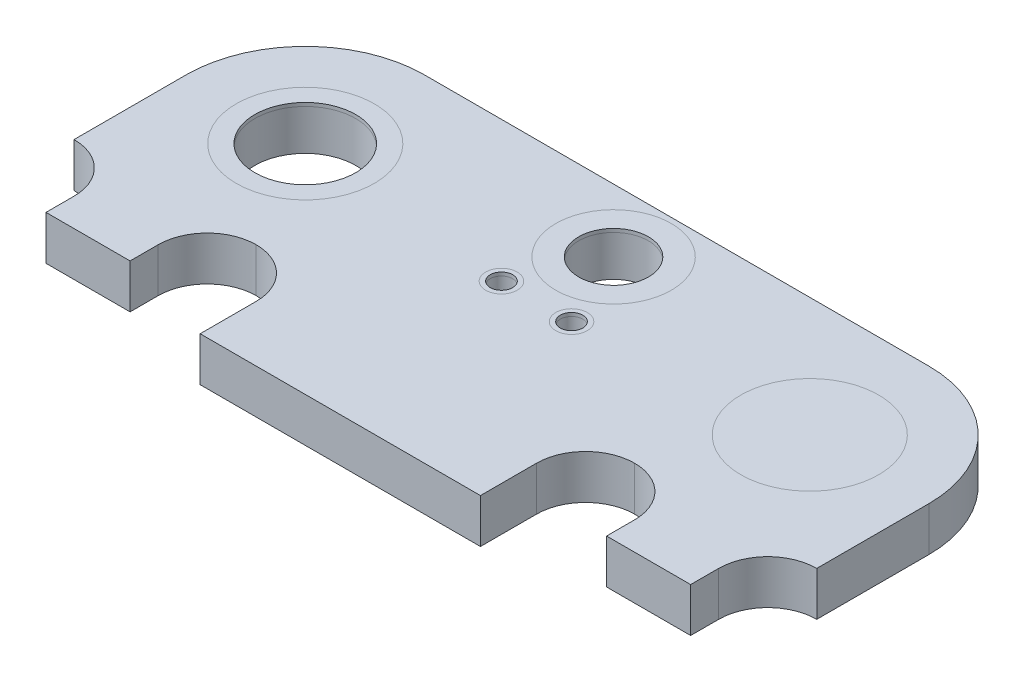
SolidWorks part; units mm, degrees
ref_plane "Front Plane" through (0, 0, 0) normal (0, 0, 1) x (1, 0, 0)
ref_plane "Battery Pins SMT Plane" through (0, 0, 0) normal (0, 1, 0) x (1, 0, 0)
ref_plane "Right Plane" through (0, 0, 0) normal (1, 0, 0) x (0, 0, -1)
ref_axis "Axis1" through (0, 0, 0) along (0, 1, 0)
sketch "Sketch1" plane through (0, 0, 0) normal (0, 1, 0) x (1, 0, 0)
  line L0 (0, 4.318) -> (0, -4.064) construction
  line L3 (-13.462, 4.318) -> (13.462, 4.318)
  line L4 (-13.462, 4.318) -> (-13.462, -4.064)
  line L5 (-13.462, -4.064) -> (13.462, -4.064)
  line L6 (13.462, 4.318) -> (13.462, -4.064)
  line L7 (-13.462, 0) -> (13.462, 0) construction
  line L8 (-5.08, -4.064) -> (-5.08, -7.874)
  line L9 (-5.08, -7.874) -> (5.08, -7.874)
  line L10 (5.08, -4.064) -> (5.08, -7.874)
  line L11 (8.636, -4.064) -> (8.636, -6.858)
  line L12 (8.636, -6.858) -> (11.684, -6.858)
  line L13 (-8.636, -4.064) -> (-8.636, -6.858)
  line L14 (-8.636, -6.858) -> (-11.684, -6.858)
  line L15 (11.684, -6.858) -> (11.684, -4.064)
  line L16 (-11.684, -6.858) -> (-11.684, -4.064)
  line L18 (9.144, 0) -> (9.144, -4.064) construction
  circle A0 centre (-9.144, 0) radius 2.5019
  circle A1 centre (9.144, 0) radius 2.5019
  arc A2 (-9.144, 4.318) -> (-13.462, 0) centre (-9.144, 0) ccw
  arc A3 (9.144, 4.318) -> (13.462, 0) centre (9.144, 0) cw
  circle A4 centre (0, 2.032) radius 1.2637
  circle A5 centre (0, 2.032) radius 2.0955
  circle A6 centre (-1.27, -0.762) radius 0.5715
  circle A7 centre (1.27, -0.762) radius 0.5715
  circle A8 centre (-1.27, -0.762) radius 0.4064
  circle A9 centre (1.27, -0.762) radius 0.4064
  circle A10 centre (-9.144, 0) radius 1.8288
  circle A11 centre (9.144, 0) radius 1.8288
  dimension "D1" = 9.144
  dimension "D3" = 5.0038
  dimension "D4" = 2.5273
  dimension "D8" = 6.858
  dimension "D11" = 4.191
  dimension "D13" = 0.762
  dimension "D14" = 1.143
  dimension "D16" = 0.8128
  dimension "D17" = 3.6576
  dimension "D2" = 4.318
  dimension "D5" = 4.064
  dimension "D6" = 7.874
  dimension "D7" = 10.16
  dimension "D9" = 3.556
  dimension "D10" = 11.684
  dimension "D12" = 2.032
  dimension "D15" = 2.54
ref_plane "PCB Rear Face" through (0, -1.6002, 0) normal (0, 1, 0) x (1, 0, 0)
sketch "Sketch2" plane through (0, 0, 0) normal (0, 1, 0) x (1, 0, 0)
  line L0 (-13.462, 4.318) -> (13.462, 4.318) construction
  line L3 (-13.462, 4.318) -> (-13.462, -4.064) construction
  line L4 (-9.144, 4.318) -> (9.144, 4.318)
  line L7 (-13.462, 0) -> (-13.462, -4.064)
  line L8 (-5.08, -4.064) -> (-5.08, -7.874) construction
  line L9 (-5.08, -4.064) -> (-5.08, -7.874)
  line L10 (-5.08, -7.874) -> (5.08, -7.874) construction
  line L11 (-5.08, -7.874) -> (5.08, -7.874)
  line L12 (5.08, -4.064) -> (5.08, -7.874) construction
  line L13 (5.08, -4.064) -> (5.08, -7.874)
  line L21 (-8.636, -4.064) -> (-8.636, -6.858) construction
  line L22 (-8.636, -4.064) -> (-8.636, -6.858)
  line L23 (-13.462, -4.064) -> (13.462, -4.064) construction
  line L24 (-13.462, -4.064) -> (-11.684, -4.064)
  line L25 (5.08, -4.064) -> (8.636, -4.064)
  line L26 (8.636, -4.064) -> (8.636, -6.858) construction
  line L27 (8.636, -4.064) -> (8.636, -6.858)
  line L28 (8.636, -6.858) -> (11.684, -6.858) construction
  line L29 (8.636, -6.858) -> (11.684, -6.858)
  line L30 (11.684, -6.858) -> (11.684, -4.064) construction
  line L31 (11.684, -6.858) -> (11.684, -4.064)
  line L36 (-11.684, -6.858) -> (-11.684, -4.064) construction
  line L37 (-11.684, -6.858) -> (-11.684, -4.064)
  line L38 (-8.636, -6.858) -> (-11.684, -6.858) construction
  line L39 (-8.636, -6.858) -> (-11.684, -6.858)
  line L40 (13.462, 4.318) -> (13.462, -4.064) construction
  line L41 (13.462, 0) -> (13.462, -4.064)
  line L42 (11.684, -4.064) -> (13.462, -4.064)
  line L43 (-8.636, -4.064) -> (-5.08, -4.064)
  arc A0 (-9.144, 4.318) -> (-13.462, 0) centre (-9.144, 0) ccw construction
  arc A1 (-9.144, 4.318) -> (-13.462, 0) centre (-9.144, 0) ccw
  arc A2 (13.462, 0) -> (9.144, 4.318) centre (9.144, 0) ccw construction
  arc A3 (13.462, 0) -> (9.144, 4.318) centre (9.144, 0) ccw
  circle A4 centre (-1.27, -0.762) radius 0.4064 construction
  circle A6 centre (-1.27, -0.762) radius 0.4064
  circle A8 centre (1.27, -0.762) radius 0.4064 construction
  circle A10 centre (0, 2.032) radius 1.2637 construction
  circle A11 centre (0, 2.032) radius 1.2637
  circle A12 centre (1.27, -0.762) radius 0.4064
  circle A13 centre (-9.144, 0) radius 1.8288 construction
  circle A14 centre (-9.144, 0) radius 1.8288
extrude "Boss-Extrude1" add sketch "Sketch2" against normal up to surface (1.6002 mm away) up to plane "PCB Rear Face"
sketch "Sketch5" plane through (0, 0, 0) normal (0, 1, 0) x (1, 0, 0)
  circle A0 centre (-9.144, 0) radius 2.5019 construction
  circle A1 centre (-9.144, 0) radius 2.5019
  circle A2 centre (9.144, 0) radius 2.5019 construction
  circle A3 centre (9.144, 0) radius 2.5019
  circle A4 centre (0, 2.032) radius 2.0955 construction
  circle A5 centre (0, 2.032) radius 2.0955
  circle A6 centre (-1.27, -0.762) radius 0.5715 construction
  circle A7 centre (-1.27, -0.762) radius 0.5715
  circle A8 centre (1.27, -0.762) radius 0.5715 construction
  circle A9 centre (1.27, -0.762) radius 0.5715
extrude "Cut-Extrude1" cut sketch "Sketch5" against normal blind 0.127
sketch "Sketch6" plane through (0, 0, 0) normal (0, 1, 0) x (1, 0, 0)
  circle A2 centre (9.144, 0) radius 2.5019 construction
  circle A3 centre (9.144, 0) radius 2.5019
  circle A4 centre (0, 2.032) radius 2.0955 construction
  circle A5 centre (0, 2.032) radius 2.0955
  circle A6 centre (0, 2.032) radius 1.2637 construction
  circle A7 centre (0, 2.032) radius 1.2637
  circle A8 centre (-1.27, -0.762) radius 0.5715 construction
  circle A9 centre (-1.27, -0.762) radius 0.5715
  circle A10 centre (1.27, -0.762) radius 0.5715 construction
  circle A11 centre (1.27, -0.762) radius 0.5715
  circle A12 centre (-1.27, -0.762) radius 0.4064 construction
  circle A13 centre (-1.27, -0.762) radius 0.4064
  circle A14 centre (1.27, -0.762) radius 0.4064 construction
  circle A15 centre (1.27, -0.762) radius 0.4064
  circle A18 centre (-9.144, 0) radius 2.5019 construction
  circle A19 centre (-9.144, 0) radius 1.8288 construction
  circle A20 centre (-9.144, 0) radius 2.5019
  circle A21 centre (-9.144, 0) radius 1.8288
extrude "Boss-Extrude2" add sketch "Sketch6" against normal up to next separate body
fillet "Fillet1" radius 1.778 6 edges at (5.08, -0.8001, 4.064) (8.636, -0.8001, 4.064) (-8.636, -0.8001, 4.064) (-11.684, -0.8001, 4.064) (-5.08, -0.8001, 4.064) (11.684, -0.8001, 4.064)
